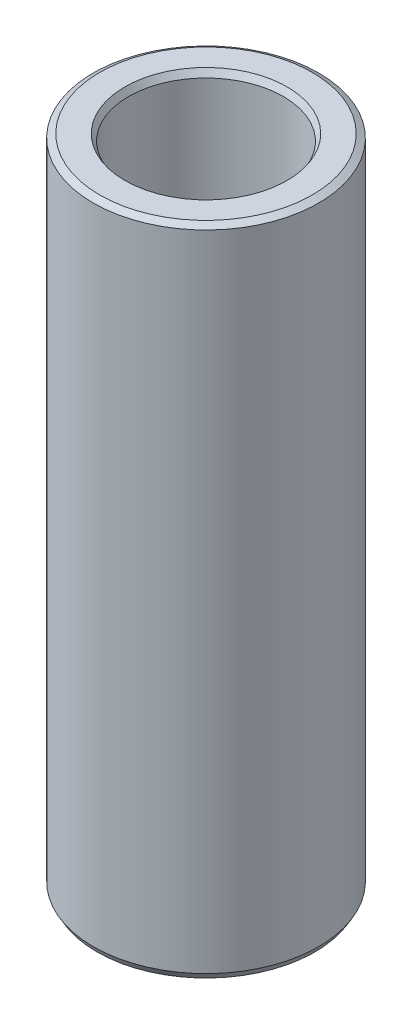
SolidWorks part; units mm, degrees
ref_plane "Front Plane" through (0, 0, 0) normal (0, 0, 1) x (1, 0, 0)
ref_plane "Top Plane" through (0, 0, 0) normal (0, 1, 0) x (1, 0, 0)
ref_plane "Right Plane" through (0, 0, 0) normal (1, 0, 0) x (0, 0, -1)
sketch "Sketch1" plane through (0, 0, 0) normal (0, 1, 0) x (1, 0, 0)
  circle A0 centre (0, 0) radius 7.5
  dimension "SLEEVE_OD" = 15
extrude "Boss-Extrude1" add sketch "Sketch1" along normal blind 43.5334
sketch "Sketch2" plane through (0, 0, 0) normal (0, 1, 0) x (1, 0, 0)
  circle A0 centre (0, 0) radius 5.1503
  dimension "BORE_D" = 10.3006
extrude "Cut-Extrude1" cut sketch "Sketch2" along normal through all
chamfer "Chamfer1" distance 0.2487 angle 60 4 edges at (0, 43.5334, 5.1503) (0, 0, 5.1503) (0, 0, 7.5) (0, 43.5334, 7.5) first distance on face at (0, 43.5334, 5.1503) first distance on face at (0, 0, 5.1503) first distance on face at (0, 43.5334, 7.5)
